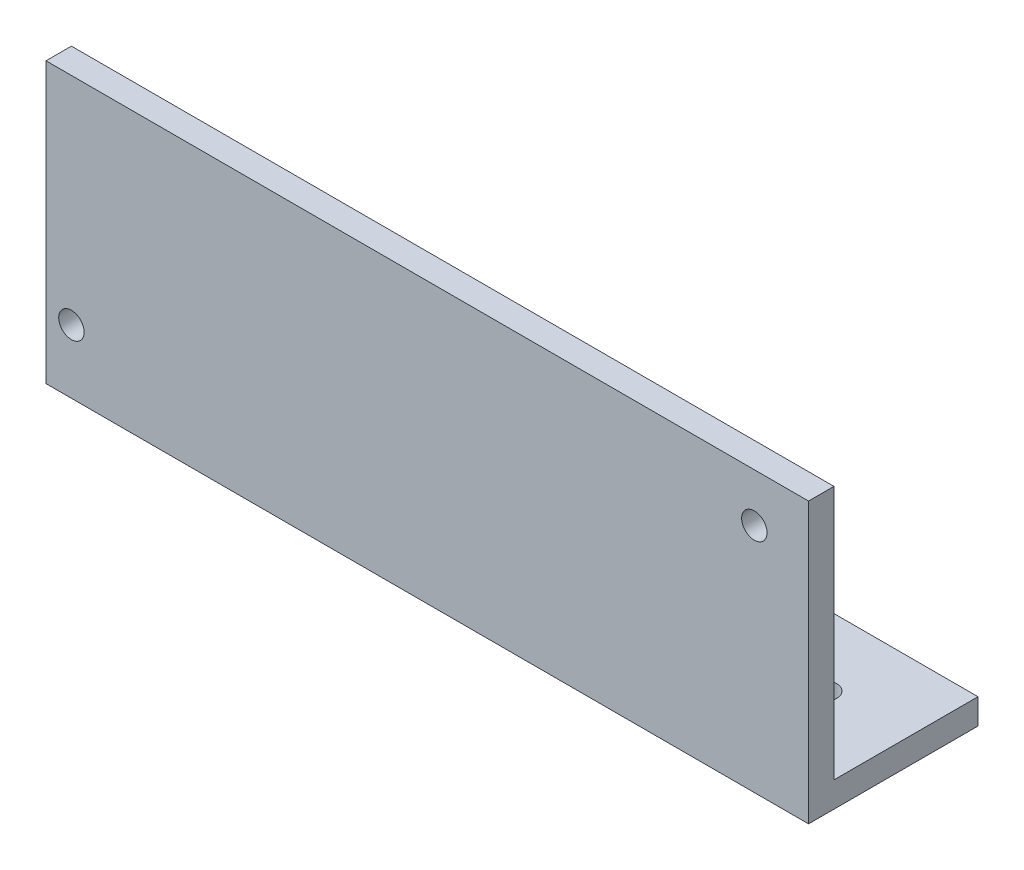
SolidWorks part; units mm, degrees
ref_plane "Front Plane" through (0, 0, 0) normal (0, 0, 1) x (1, 0, 0)
ref_plane "Top Plane" through (0, 0, 0) normal (0, 1, 0) x (1, 0, 0)
ref_plane "Right Plane" through (0, 0, 0) normal (1, 0, 0) x (0, 0, -1)
sketch "Sketch1" plane through (0, 0, 0) normal (0, 1, 0) x (1, 0, 0)
  line L0 (-13.8565, -4.4888) -> (76.1435, -4.4888) construction
  line L1 (-13.8565, -7.4888) -> (76.1435, -7.4888)
  line L2 (-13.8565, -7.4888) -> (-13.8565, 12.5112)
  line L3 (-13.8565, 12.5112) -> (76.1435, 12.5112)
  line L4 (76.1435, -7.4888) -> (76.1435, 12.5112)
  line L5 (-9.7129, 12.5112) -> (-9.7129, -4.4888) construction
  circle A0 centre (-6.3381, 4.0112) radius 1.5
  circle A1 centre (66.471, 4.0112) radius 1.5
  point P10 (0, 0)
  point P13 (-9.7129, 4.0112)
  point P14 (0, 0)
  dimension "D3" = 3
  dimension "D4" = 3
  dimension "D1" = 90
  dimension "D2" = 20
  dimension "D5" = 3
extrude "Boss-Extrude1" add sketch "Sketch1" along normal blind 3
sketch "Sketch2" plane through (0, 0, 7.4888) normal (0, 0, 1) x (1, 0, 0)
  line L0 (76.1435, 3) -> (76.1435, 0) construction
  line L1 (-13.8565, 3) -> (76.1435, 3)
  line L2 (-13.8565, 3) -> (-13.8565, 33)
  line L3 (-13.8565, 33) -> (76.1435, 33)
  line L4 (76.1435, 3) -> (76.1435, 33)
  circle A0 centre (-10.8565, 7.5) radius 1.5
  circle A1 centre (69.7435, 27.3) radius 1.5
  dimension "D2" = 3
  dimension "D3" = 3
  dimension "D1" = 30
  dimension "D4" = 4.5
  dimension "D5" = 3
  dimension "D6" = 80.6
  dimension "D7" = 19.8
extrude "Boss-Extrude2" add sketch "Sketch2" against normal blind 3
